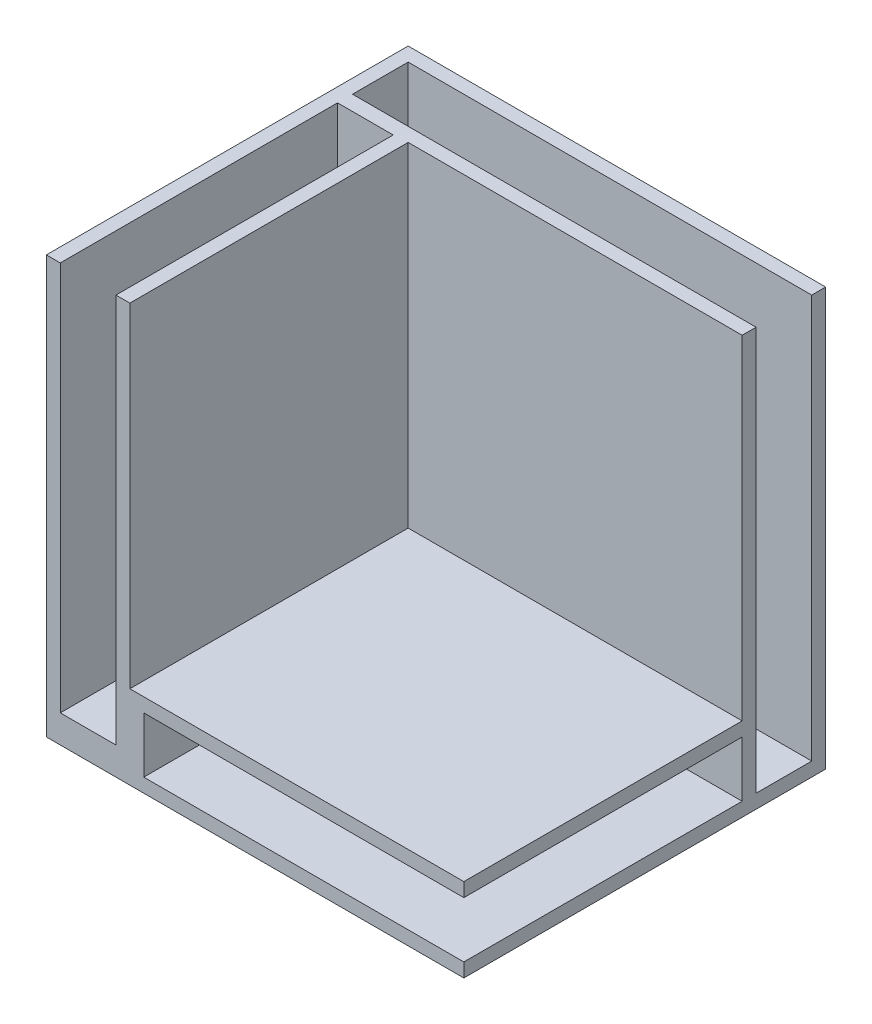
SolidWorks part; units mm, degrees
ref_plane "Front Plane" through (0, 0, 0) normal (0, 0, 1) x (1, 0, 0)
ref_plane "Top Plane" through (0, 0, 0) normal (0, 1, 0) x (1, 0, 0)
ref_plane "Right Plane" through (0, 0, 0) normal (1, 0, 0) x (0, 0, -1)
sketch "Sketch1" plane through (0, 0, 0) normal (0, 0, 1) x (1, 0, 0)
  line L1 (0, 0) -> (30, 0)
  line L2 (0, 0) -> (0, 30)
  line L3 (0, 30) -> (30, 30)
  line L4 (30, 0) -> (30, 30)
  dimension "D1" = 30
  dimension "D2" = 30
extrude "Boss-Extrude1" add sketch "Sketch1" along normal blind 6
sketch "Sketch2" plane through (0, 0, 6) normal (0, 0, 1) x (1, 0, 0)
  line L0 (0, 0) -> (30, 0) construction
  line L5 (6, 6) -> (0, 6)
  line L6 (30, 0) -> (6, 0)
  line L7 (30, 0) -> (30, 6)
  line L8 (30, 6) -> (6, 6)
  line L9 (6, 0) -> (6, 6)
  line L10 (6, 6) -> (6, 30)
  line L11 (30, 30) -> (0, 30) construction
  line L12 (6, 30) -> (0, 30)
  line L13 (0, 30) -> (0, 6)
  line L15 (5, 6) -> (6, 6)
  line L16 (5, 6) -> (5, 5)
  line L17 (5, 5) -> (6, 5)
  line L18 (6, 6) -> (6, 5)
  line M7 (0, 30) -> (0, 0)
  line M10 (30, 30) -> (0, 30)
  dimension "D1" = 6
  dimension "D2" = 6
  dimension "D3" = 1
  dimension "D4" = 1
extrude "Boss-Extrude4" add sketch "Sketch2" along normal blind 20 contours L5 L10 M10 M7 region at (3, 18, 6)
sketch "Sketch3" plane through (0, 0, 6) normal (0, 0, 1) x (1, 0, 0)
  line L1 (30, 0) -> (6, 0)
  line L2 (30, 0) -> (30, 6)
  line L3 (30, 6) -> (6, 6)
  line L4 (6, 0) -> (6, 6)
sketch "Sketch4" plane through (0, 0, 6) normal (0, 0, 1) x (1, 0, 0)
  line L1 (6, 6) -> (4, 6)
  line L2 (6, 6) -> (6, 4)
  line L3 (6, 4) -> (4, 4)
  line L4 (4, 6) -> (4, 4)
  dimension "D1" = 2
  dimension "D2" = 2
extrude "Boss-Extrude6" add sketch "Sketch4" along normal blind 20
sketch "Sketch5" plane through (0, 0, 6) normal (0, 0, 1) x (1, 0, 0)
  line L1 (6, 6) -> (30, 6)
  line L2 (6, 6) -> (6, 0)
  line L3 (6, 0) -> (30, 0)
  line L4 (30, 6) -> (30, 0)
extrude "Boss-Extrude7" add sketch "Sketch5" along normal blind 20
sketch "Sketch6" plane through (0, 0, 0) normal (0, 0, -1) x (-1, 0, 0)
  line L4 (0, 0) -> (0, 30)
  line L5 (0, 30) -> (-30, 30)
  line L6 (-30, 30) -> (-30, 0)
  line L7 (-30, 0) -> (0, 0)
  line L8 (0, 0) -> (0, 30)
  line L9 (0, 30) -> (-30, 30)
  line L10 (-30, 30) -> (-30, 0)
  line L11 (-30, 0) -> (0, 0)
  dimension "D1" = 0
shell "Shell2" thickness 1 removed face at (12, 30, 10.6667) removed face at (30, 12, 10.6667)
sketch "Sketch7" plane through (0, 5, 0) normal (0, -1, 0) x (1, 0, 0)
  line L1 (30, 5) -> (7, 5)
  line L2 (30, 5) -> (30, 6)
  line L3 (30, 6) -> (7, 6)
  line L4 (7, 5) -> (7, 6)
  dimension "D1" = 23
  dimension "D2" = 1
extrude "Boss-Extrude8" add sketch "Sketch7" along normal blind 5
sketch "Sketch8" plane through (0, 0, 6) normal (0, 0, 1) x (1, 0, 0)
  line L4 (6, 6) -> (30, 6)
  line L5 (30, 6) -> (30, 30)
  line L6 (30, 30) -> (6, 30)
  line L7 (6, 30) -> (6, 6)
  line L8 (6, 6) -> (30, 6)
  line L9 (30, 6) -> (30, 30)
  line L10 (30, 30) -> (6, 30)
  line L11 (6, 30) -> (6, 6)
  dimension "D1" = 0
sketch "Sketch9" plane through (5, 0, 0) normal (-1, 0, 0) x (0, 0, 1)
  line L1 (5, 30) -> (6.0751, 30)
  line L2 (5, 30) -> (5, 7)
  line L3 (5, 7) -> (6.0751, 7)
  line L4 (6.0751, 30) -> (6.0751, 7)
  dimension "D1" = 23
  dimension "D2" = 1.0751
extrude "Boss-Extrude9" add sketch "Sketch9" along normal blind 5
sketch "Sketch10" plane through (0, 0, 26) normal (0, 0, 1) x (1, 0, 0)
  line L0 (0, 30) -> (0, 6) construction
  line L1 (1, 7) -> (5, 7)
  line L2 (1, 7) -> (1, 30)
  line L3 (1, 30) -> (5, 30)
  line L4 (5, 7) -> (5, 30)
  line L6 (4, 6) -> (0, 6) construction
  dimension "D1" = 1
  dimension "D2" = 1
extrude "Cut-Extrude1" cut sketch "Sketch10" against normal blind 10
sketch "Sketch11" plane through (0, 0, 26) normal (0, 0, 1) x (1, 0, 0)
  line L0 (30, 0) -> (30, 6) construction
  line L1 (7, 5) -> (30, 5)
  line L2 (7, 5) -> (7, 1)
  line L3 (7, 1) -> (30, 1)
  line L4 (30, 5) -> (30, 1)
  line L5 (30, 6) -> (6, 6) construction
  line L6 (30, 0) -> (6, 0) construction
  line L7 (6, 0) -> (6, 6) construction
  point P12 (6, 3)
  dimension "D1" = 1
  dimension "D2" = 1
  dimension "D3" = 1
extrude "Cut-Extrude2" cut sketch "Sketch11" against normal blind 10
sketch "Sketch12" plane through (0, 0, 6) normal (0, 0, 1) x (1, 0, 0)
  line L6 (6, 0) -> (6, 4)
  line L7 (6, 4) -> (4, 4)
  line L8 (4, 4) -> (4, 6)
  line L9 (4, 6) -> (0, 6)
  line L10 (0, 6) -> (0, 0)
  line L11 (0, 0) -> (6, 0)
  line L12 (6, 0) -> (6, 4)
  line L13 (6, 4) -> (4, 4)
  line L14 (4, 4) -> (4, 6)
  line L15 (4, 6) -> (0, 6)
  line L16 (0, 6) -> (0, 0)
  line L17 (0, 0) -> (6, 0)
  dimension "D1" = 0
extrude "Boss-Extrude11" add sketch "Sketch12" along normal blind 20
sketch "Sketch14" plane through (0, 7, 0) normal (0, 1, 0) x (1, 0, 0)
  line L4 (5, -6.0751) -> (1, -6.0751)
  line L5 (1, -6.0751) -> (1, -26)
  line L6 (1, -26) -> (5, -26)
  line L7 (5, -26) -> (5, -6.0751)
  line L8 (5, -6.0751) -> (1, -6.0751)
  line L9 (1, -6.0751) -> (1, -26)
  line L10 (1, -26) -> (5, -26)
  line L11 (5, -26) -> (5, -6.0751)
  dimension "D1" = 0
extrude "Cut-Extrude4" cut sketch "Sketch14" against normal blind 5
